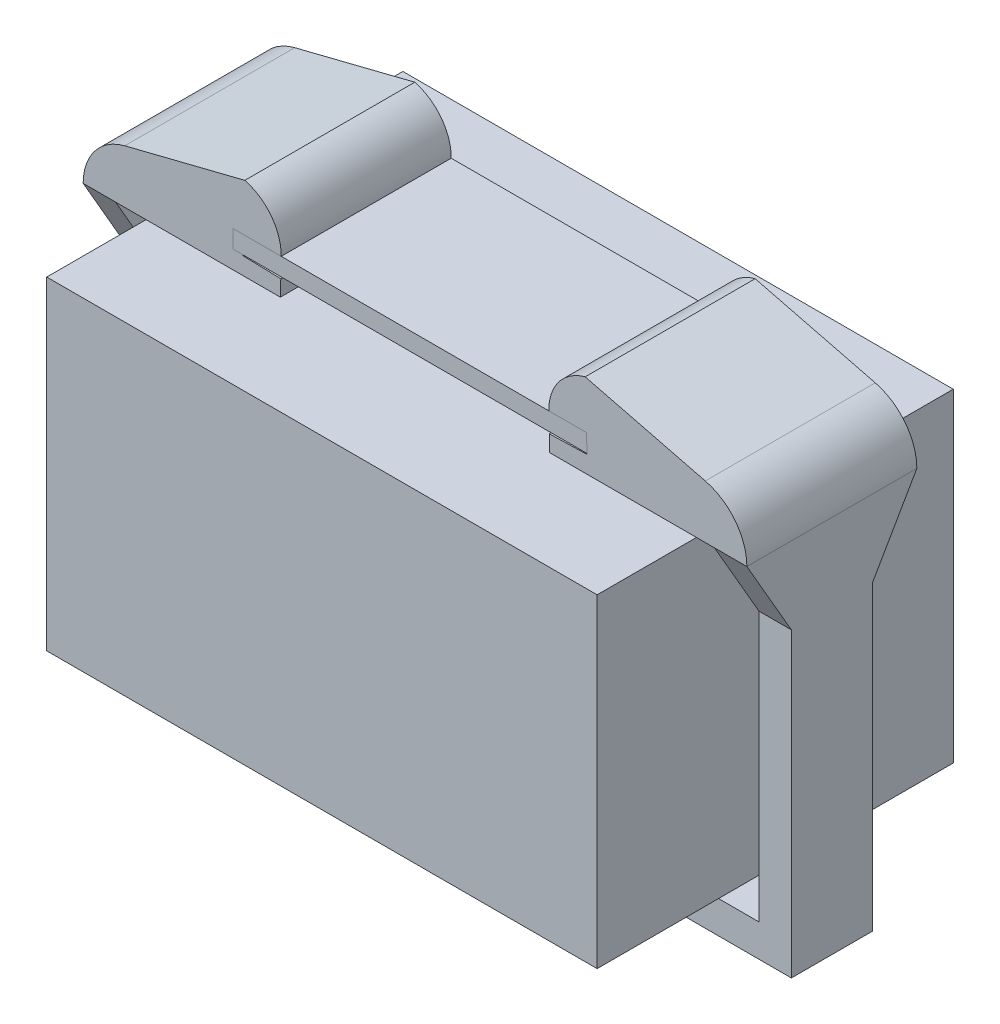
SolidWorks part; units mm, degrees
ref_plane "Front Plane" through (0, 0, 0) normal (0, 0, 1) x (1, 0, 0)
ref_plane "Top Plane" through (0, 0, 0) normal (0, 1, 0) x (1, 0, 0)
ref_plane "Right Plane" through (0, 0, 0) normal (1, 0, 0) x (0, 0, -1)
sketch "Sketch1" plane through (0, 0, 0) normal (0, 1, 0) x (1, 0, 0)
  line L9 (-22.5, -10.5) -> (22.5, -10.5)
  line L10 (-22.5, -10.5) -> (-22.5, 10.5)
  line L11 (-22.5, 10.5) -> (22.5, 10.5)
  line L12 (22.5, -10.5) -> (22.5, 10.5)
  line L13 (-22.5, -10.5) -> (22.5, 10.5) construction
  line L14 (-22.5, 10.5) -> (22.5, -10.5) construction
  point P0 (0, 0)
  point P7 (0, 0)
  dimension "D2" = 21
  dimension "D3" = 45
extrude "Boss-Extrude1" add sketch "Sketch1" along normal blind 2.2
ref_plane "Plane1" through (0, -3, 0) normal (0, -1, 0) x (-1, 0, 0)
sketch "Sketch2" plane through (0, -3, 0) normal (0, 1, 0) x (1, 0, 0)
  line L1 (-34, -22) -> (34, -22)
  line L2 (-34, -22) -> (-34, 22)
  line L3 (-34, 22) -> (34, 22)
  line L4 (34, -22) -> (34, 22)
  line L5 (-34, -22) -> (34, 22) construction
  line L6 (-34, 22) -> (34, -22) construction
  point P0 (0, 0)
  dimension "D1" = 44
  dimension "D2" = 68
extrude "Boss-Extrude2" add sketch "Sketch2" against normal blind 40 separate body
sketch "Sketch3" plane through (0, 0, 0) normal (0, 0, 1) x (1, 0, 0)
  line L0 (-34, -43) -> (34, -43) construction
  line L1 (-21.25, -57.7) -> (21.25, -57.7) construction
  line L2 (-21.25, -57.7) -> (-21.25, -45) construction
  line L3 (-21.25, -45) -> (21.25, -45) construction
  line L4 (21.25, -57.7) -> (21.25, -45) construction
  line L5 (-21.25, -57.7) -> (21.25, -45) construction
  line L6 (-21.25, -45) -> (21.25, -57.7) construction
  line L7 (22.5, 2.2) -> (22.5, 0) construction
  line L8 (0, -24.2) -> (0, 24.2) construction
  line L10 (21.25, -57.7) -> (25.25, -57.7) construction
  line L11 (21.25, -57.7) -> (21.25, 0) construction
  line L13 (25.25, -57.7) -> (25.25, 0) construction
  line L16 (-25.25, -57.7) -> (-25.25, 0) construction
  line L17 (-21.25, -57.7) -> (-25.25, -57.7) construction
  line L18 (-21.25, -57.7) -> (-21.25, 0) construction
  line L20 (21.25, -45) -> (22.5, 0) construction
  line L21 (24.2, 0) -> (-24.2, 0) construction
  line L22 (25.25, 0) -> (25.0223, 8.1968) construction
  line L23 (25.25, 0) -> (25.25, 5.5196)
  line L24 (25.0223, 8.1968) -> (21.0239, 8.0858) construction
  line L26 (21.25, 0) -> (21.1889, 2.1992) construction
  line L27 (16.5239, 2.0696) -> (21.1889, 2.1992) construction
  line L28 (-21.25, 0) -> (-21.1889, 2.1992) construction
  line L29 (-16.5239, 2.0696) -> (-21.1889, 2.1992) construction
  line L30 (-25.25, 0) -> (-25.0223, 8.1968) construction
  line L31 (-25.0223, 8.1968) -> (-21.0239, 8.0858) construction
  circle A2 centre (0, -51.35) radius 2.5 construction
  arc A3 (21.0239, 8.0858) -> (16.5239, 2.0696) centre (22.5709, 2.2375) ccw construction
  arc A4 (-21.0239, 8.0858) -> (-16.5239, 2.0696) centre (-22.5709, 2.2375) cw construction
  point P0 (0, -51.35)
  dimension "D8" = 5
  dimension "D1" = 2
  dimension "D2" = 12.7
  dimension "D3" = 1.25
  dimension "D7" = 4
  dimension "D9" = 1.591
  dimension "D4" = 8.2
  dimension "D5" = 1.591
  dimension "D6" = 4.5
  dimension "D10" = 2.2
sketch "Sketch4" plane through (0, 0, 0) normal (0, 0, 1) x (1, 0, 0)
  line L1 (-37, -45) -> (37, -45)
  line L2 (-37, -45) -> (-37, -49)
  line L3 (-37, -49) -> (-25.25, -49)
  line L4 (37, -45) -> (37, -49)
  line L5 (34, -43) -> (34, -3) construction
  line L6 (-34, -43) -> (34, -43) construction
  line L7 (21.0239, 8.0858) -> (35.8626, 4.3619)
  line L8 (37, -49) -> (41, -49)
  line L9 (37, -49) -> (37, -2.2241)
  line L11 (41, -49) -> (41, -2.2241)
  line L12 (22.5, 0) -> (22.5, -45) construction
  line L13 (16.5239, 2.0696) -> (21.1889, 2.1992) construction
  line L14 (-25.25, -57.7) -> (-25.25, 0) construction
  line L16 (16.5239, 2.0696) -> (21.1889, 2.1992)
  line L17 (0, -24.2) -> (0, 24.2) construction
  line L19 (21.1889, 2.1992) -> (21.25, -0.1008)
  line L20 (21.25, -57.7) -> (21.25, 0) construction
  line L21 (21.25, -0.1008) -> (16.5848, -0.2248)
  line L22 (16.5848, -0.2248) -> (16.6379, -2.2241)
  line L23 (16.6379, -2.2241) -> (37, -2.2241)
  line L24 (2.1213, -49) -> (37, -49)
  line L25 (37, -49) -> (25.25, -49)
  line L26 (37, -2.2241) -> (41, -2.2241)
  line L27 (-37, -49) -> (-41, -49)
  line L28 (-41, -49) -> (-41, -2.2241)
  line L29 (-37, -49) -> (-37, -2.2241)
  line L30 (-37, -2.2241) -> (-41, -2.2241)
  line L31 (-16.6379, -2.2241) -> (-37, -2.2241)
  line L32 (-16.5848, -0.2248) -> (-16.6379, -2.2241)
  line L33 (-21.25, -0.1008) -> (-16.5848, -0.2248)
  line L34 (-21.1889, 2.1992) -> (-21.25, -0.1008)
  line L35 (-16.5239, 2.0696) -> (-21.1889, 2.1992)
  line L36 (-21.0239, 8.0858) -> (-35.8626, 4.3619)
  line L37 (-41, -2.2241) -> (-37, -2.2241) construction
  arc A2 (21.0239, 8.0858) -> (16.5239, 2.0696) centre (22.5709, 2.2375) ccw construction
  arc A3 (35.8626, 4.3619) -> (41, -2.2241) centre (34.2098, -2.2241) cw
  arc A4 (21.0239, 8.0858) -> (16.5239, 2.0696) centre (22.5709, 2.2375) ccw
  arc A5 (-25.25, -49) -> (25.25, -49) centre (0, 6.2102) ccw
  circle A6 centre (0, -49.75) radius 2.25
  arc A7 (-21.0239, 8.0858) -> (-16.5239, 2.0696) centre (-22.5709, 2.2375) cw
  arc A8 (-35.8626, 4.3619) -> (-41, -2.2241) centre (-34.2098, -2.2241) ccw
  point P38 (0, -54.5)
  dimension "D9" = 4.5
  dimension "D10" = 2.5
  dimension "D11" = 2.5
  dimension "D1" = 2
  dimension "D2" = 3
  dimension "D4" = 4
  dimension "D5" = 2.7902
  dimension "D6" = 4
  dimension "D7" = 2.3
  dimension "D8" = 2
extrude "Boss-Extrude3" add sketch "Sketch4" along normal blind 5 and the other way blind 5 separate body contours L29 L30 L28 L27 L2 | A6 L24 L4 L1 L2 L3 A5 | L26 L9 L4 L8 L11 region at (0, -45.7461, 0) region at (-39, -25.612, 0) region at (39, -25.612, 0)
extrude "Boss-Extrude4" add sketch "Sketch4<4>" along normal up to vertex (-10.5 mm away) and the other way up to vertex (10.5 mm away) contours L7 A4 L16 L19 L21 L22 L23 L26 A3 | L36 A8 L30 L31 L32 L33 L34 L35 A7 region at (-27.8947, 1.9543, 0) region at (27.8947, 1.9543, 0) up to point (22.5, 0, -10.5) other way up to point (22.5, 0, -10.5)
sketch "Sketch4<4>" plane through (0, 0, 0) normal (0, 0, 1) x (1, 0, 0) same geometry as "Sketch4"
sketch "Sketch6" plane through (41, 0, 0) normal (1, 0, 0) x (0, 0, -1)
  line L0 (10.5, -2.2241) -> (5, -11.7503)
  line L1 (5, -49) -> (5, -2.2241) construction
  line L2 (5, -11.7503) -> (5, -2.2241)
  line L3 (5, -2.2241) -> (10.5, -2.2241)
  line L4 (0, 36.2439) -> (0, -36.2439) construction
  line L5 (-5, -11.7503) -> (-5, -2.2241)
  line L6 (-10.5, -2.2241) -> (-5, -11.7503)
  line L7 (-5, -2.2241) -> (-10.5, -2.2241)
  dimension "D1" = 30
extrude "Boss-Extrude5" add sketch "Sketch6" against normal up to vertex (4 mm away) up to point (37, -2.2241, -5)
mirror "Mirror1" about plane through (0, 0, 0) normal (1, 0, 0) of "Boss-Extrude5"
equation "\"D5@Sketch3\"=\"D9@Sketch3\""
